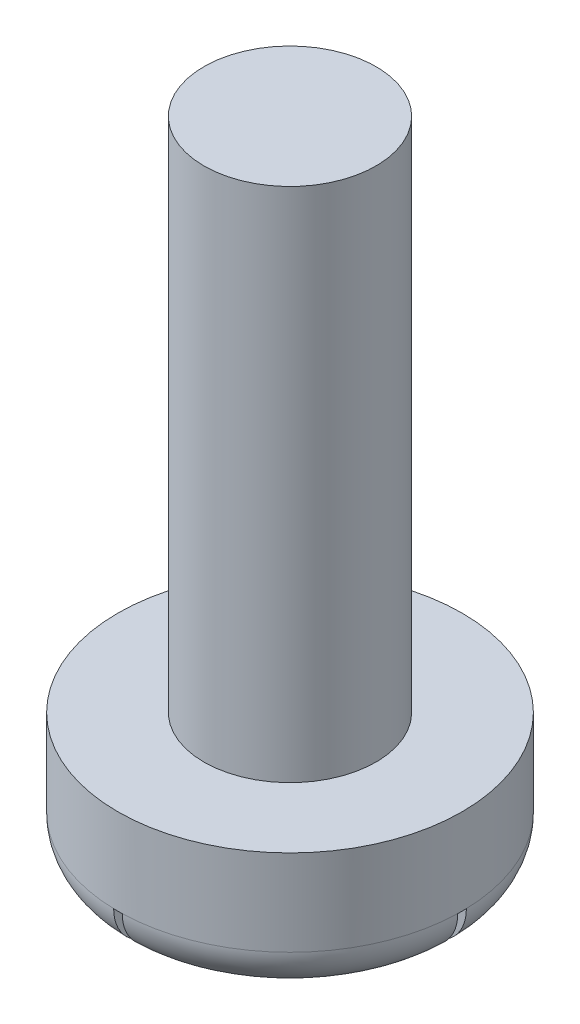
SolidWorks part; units mm, degrees
ref_plane "前视基准面" through (0, 0, 0) normal (0, 0, 1) x (1, 0, 0)
ref_plane "上视基准面" through (0, 0, 0) normal (0, 1, 0) x (1, 0, 0)
ref_plane "右视基准面" through (0, 0, 0) normal (1, 0, 0) x (0, 0, -1)
other "Configuration Table"
sketch "草图1" plane through (0, 0, 0) normal (0, 1, 0) x (1, 0, 0)
  circle A0 centre (0, 0) radius 4
  dimension "D1" = 8
extrude "凸台-拉伸1" add sketch "草图1" against normal blind 3
sketch "草图2" plane through (0, 0, 0) normal (0, 1, 0) x (1, 0, 0)
  circle A0 centre (0, 0) radius 2
  dimension "D1" = 4
extrude "凸台-拉伸2" add sketch "草图2" along normal blind 12 contours A0
sketch "草图4" plane through (0, -3, 0) normal (0, -1, 0) x (1, 0, 0)
  line L0 (-4, 0) -> (4, 0)
  line L1 (0, 4) -> (0, -4)
  circle A1 centre (0, 0) radius 4 construction
extrude "切除-拉伸-薄壁1" cut sketch "草图4" against normal blind 1 and the other way through all thin thin type mid plane wall 0.2
ref_axis "基准轴1" through (0, 23.8772, 0) along (0, -1, 0)
fillet "圆角1" radius 1 4 edges at (2.8284, -3, 2.8284) (-2.8284, -3, 2.8284) (-2.8284, -3, -2.8284) (2.8284, -3, -2.8284)
